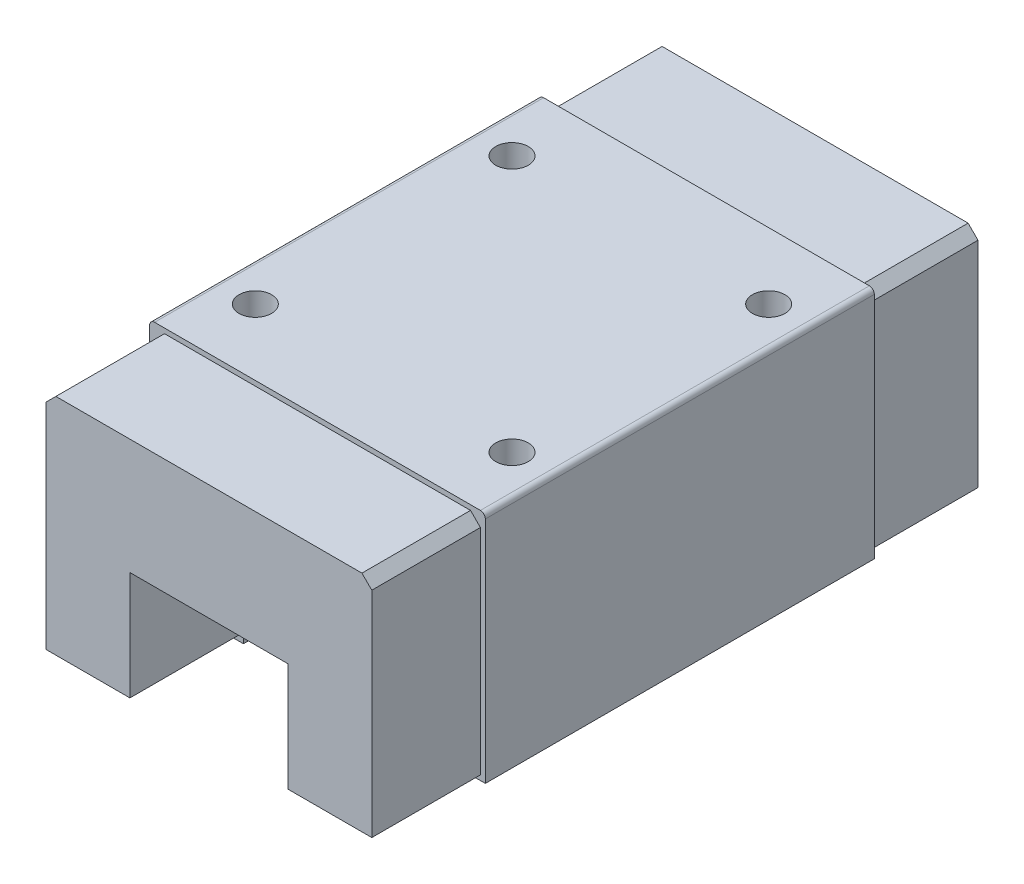
SolidWorks part; units mm, degrees
ref_plane "Front Plane" through (0, 0, 0) normal (0, 0, 1) x (1, 0, 0)
ref_plane "Top Plane" through (0, 0, 0) normal (0, 1, 0) x (1, 0, 0)
ref_plane "Right Plane" through (0, 0, 0) normal (1, 0, 0) x (0, 0, -1)
sketch "Sketch1" plane through (0, 0, 0) normal (0, 0, 1) x (1, 0, 0)
  line L0 (0, -29.376) -> (0, 29.376) construction
  line L1 (17, 0) -> (-17, 0)
  line L2 (-17, 0) -> (-17, -23.7)
  line L3 (-17, -23.7) -> (-7.5, -23.7)
  line L4 (-7.5, -23.7) -> (-7.5, -12.7)
  line L5 (-7.5, -12.7) -> (7.5, -12.7)
  line L6 (7.5, -23.7) -> (7.5, -12.7)
  line L7 (17, -23.7) -> (7.5, -23.7)
  line L8 (17, 0) -> (17, -23.7)
  point P4 (0, 0)
  point P14 (0, -12.7)
  point P16 (0, 0)
  dimension "D1" = 17
  dimension "D2" = 23.7
  dimension "D3" = 11
  dimension "D4" = 7.5
extrude "Boss-Extrude1" add sketch "Sketch1" along normal mid plane 39.4
sketch "Sketch2" plane through (0, 0, 0) normal (0, 0, 1) x (1, 0, 0)
  line L0 (-16.5, -0.5) -> (-16.5, -23.2)
  line L1 (-16.5, -23.2) -> (-8, -23.2)
  line L2 (-8, -23.2) -> (-8, -12.2)
  line L3 (-8, -12.2) -> (8, -12.2)
  line L4 (0, 0) -> (0, -16.1431) construction
  line L5 (-16.5, -0.5) -> (16.5, -0.5)
  line L6 (-17, 0) -> (-17, -23.7) construction
  line L7 (-17, -23.7) -> (-7.5, -23.7) construction
  line L8 (-7.5, -23.7) -> (-7.5, -12.7) construction
  line L9 (-7.5, -12.7) -> (7.5, -12.7) construction
  line L10 (17, 0) -> (-17, 0) construction
  line L11 (16.5, -23.2) -> (8, -23.2)
  line L12 (8, -23.2) -> (8, -12.2)
  line L13 (16.5, -0.5) -> (16.5, -23.2)
  point P22 (0, -12.2)
  point P23 (0, -0.5)
  dimension "D1" = 0.5
  dimension "D2" = 0.5
  dimension "D3" = 0.5
  dimension "D4" = 0.5
  dimension "D5" = 0.5
extrude "Boss-Extrude2" add sketch "Sketch2" along normal mid plane 61.4
sketch "Sketch3" plane through (0, 0, 0) normal (0, 0, 1) x (1, 0, 0)
  line L0 (-7.5, -11.8323) -> (-7.5, -2.3465) construction
  line L1 (-7.5, -23.7) -> (-7.5, -12.7) construction
  line L2 (-17, -23.7) -> (-7.5, -23.7) construction
  line L3 (-7.5, -14.7) -> (-7.5, -17.7)
  arc A0 (-7.5, -14.7) -> (-7.5, -17.7) centre (-7.5, -16.2) cw
  dimension "D1" = 1.5
  dimension "D2" = 7.5
revolve "Revolve1" add sketch "Sketch3" angle 360 about L0
mirror "Mirror1" about plane through (0, 0, 0) normal (1, 0, 0) of "Revolve1"
pattern_linear "LPattern1" count 5 spacing 4 along (0, 0, -1) of "Mirror1"
mirror "Mirror2" about plane through (0, 0, 0) normal (0, 0, 1) of "LPattern1"
sketch "Sketch4" plane through (0, 0, 0) normal (0, 1, 0) x (1, 0, 0)
  line L0 (0, 0) -> (17, 0) construction
  line L1 (17, -19.7) -> (17, 19.7) construction
  line L2 (0, 0) -> (0, 19.7) construction
  line L3 (17, 19.7) -> (-17, 19.7) construction
  circle A0 centre (13, 13) radius 3.3441
  circle A1 centre (13, -13) radius 3.3441
  circle A2 centre (-13, -13) radius 3.3441
  circle A3 centre (-13, 13) radius 3.3441
  dimension "D1" = 13
  dimension "D2" = 4
hole_wizard "M4 Tapped Hole1" positions "3DSketch1" profile "Sketch5" tap size "M4" standard "GB"
sketch3d "3DSketch1"
  point P0 (-13, 0, -13)
  point P3 (-13, 0, 13)
  point P6 (13, 0, 13)
  point P9 (13, 0, -13)
sketch "Sketch5" plane through (-13, 0, -13) normal (1, 0, 0) x (0, 0, 1)
  line L0 (0, 0) -> (0, 6.9914)
  line L1 (0, 6.9914) -> (1.65, 6)
  line L2 (1.65, 6) -> (1.65, 0)
  line L5 (1.65, 0) -> (0, 0)
  line L10 (0, 6.9914) -> (-1.65, 6) construction
  line L11 (0, -6.35) -> (0, 107.95) construction
  dimension "Tap Drill Dia." = 3.3
  dimension "Tap Drill Depth" = 6
  dimension "Drill Angle" = 118
cosmetic thread "Hole Thread1" parameters "D1"=5, "D2"=4
cosmetic thread "Hole Thread2" parameters "D1"=5, "D2"=4
cosmetic thread "Hole Thread3" parameters "D1"=5, "D2"=4
cosmetic thread "Hole Thread4" parameters "D1"=5, "D2"=4
chamfer "Chamfer1" distance 1 angle 45 4 edges at (-16.5, -0.5, -25.2) (16.5, -0.5, -25.2) (16.5, -0.5, 25.2) (-16.5, -0.5, 25.2)
fillet "Fillet1" radius 0.5 2 edges at (17, 0, 0) (-17, 0, 0)
